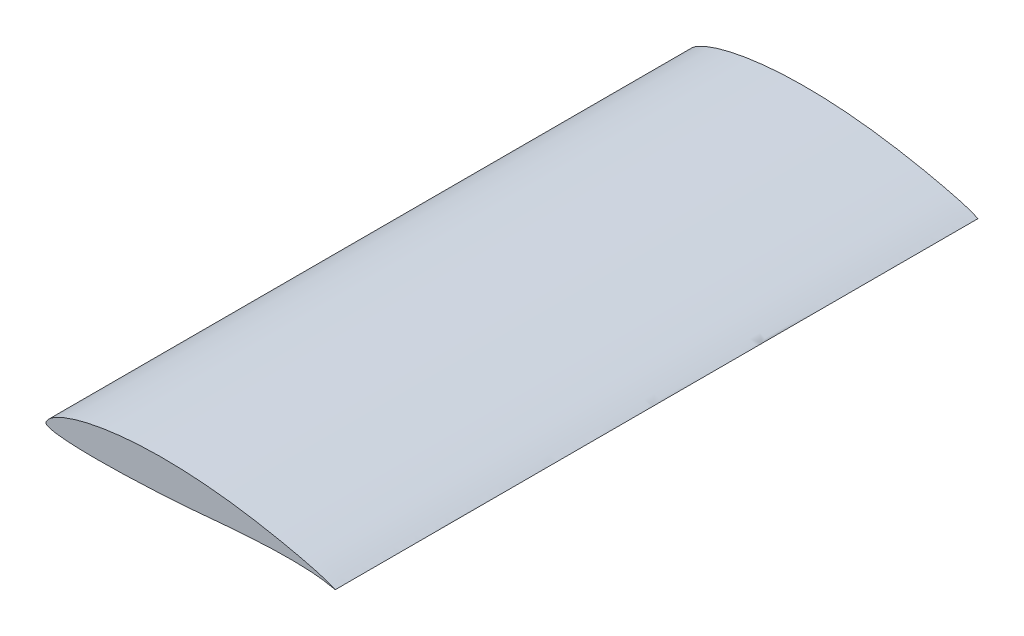
SolidWorks part; units mm, degrees
material "polystirene foam"
ref_plane "Front Plane" through (0, 0, 0) normal (0, 0, 1) x (1, 0, 0)
ref_plane "Top Plane" through (0, 0, 0) normal (0, 1, 0) x (1, 0, 0)
ref_plane "Right Plane" through (0, 0, 0) normal (1, 0, 0) x (0, 0, -1)
curve "Curve1"
  spline degree 3 poles (267.933, 0.5337, 0) (270.49, -0.1564, 0) (268.2375, 0.6665, 0) (266.5672, 1.4668, 0) (262.6756, 3.0154, 0) (257.9132, 4.5724, 0) (251.732, 6.3325, 0) (244.4112, 8.2376, 0) (235.9576, 10.2728, 0) (226.5142, 12.3893, 0) (216.1934, 14.5409, 0) (205.1313, 16.6775, 0) (193.4567, 18.7298, 0) (181.2977, 20.6324, 0) (168.7678, 22.3117, 0) (155.9753, 23.7079, 0) (143.0353, 24.8049, 0) (130.0617, 25.5802, 0) (117.1734, 26.0003, 0) (104.4837, 26.0576, 0) (92.1044, 25.7531, 0) (80.1395, 25.0742, 0) (68.69, 24.0381, 0) (57.8509, 22.6699, 0) (47.7143, 21.0125, 0) (38.3732, 19.0872, 0) (29.9084, 16.9558, 0) (22.399, 14.6444, 0) (15.9079, 12.2159, 0) (10.4843, 9.7202, 0) (6.177, 7.2209, 0) (2.9612, 4.7412, 0) (0.9766, 2.4261, 0) (0.0237, 0.7907, 0) (-0.0162, -0.4697, 0) (0.8003, -1.8361, 0) (3.4921, -2.6295, 0) (7.308, -3.6627, 0) (12.6566, -4.3991, 0) (19.3194, -5.0329, 0) (27.2905, -5.4698, 0) (36.4622, -5.7387, 0) (46.7414, -5.84, 0) (58.0105, -5.7702, 0) (70.1434, -5.5368, 0) (83.0071, -5.1408, 0) (96.4629, -4.5659, 0) (110.374, -3.827, 0) (124.6167, -2.893, 0) (139.0995, -1.7363, 0) (153.7348, -0.4008, 0) (168.4097, 0.8923, 0) (182.9339, 2.0414, 0) (197.0782, 2.9592, 0) (210.6044, 3.579, 0) (223.2667, 3.8744, 0) (234.8405, 3.8186, 0) (245.0477, 3.4533, 0) (253.7786, 2.7629, 0) (260.4407, 1.9422, 0) (265.7815, 0.9299, 0) (267.933, 0.5337, 0) (270.49, -0.1564, 0) (268.2375, 0.6665, 0) knots -0.016249 -0.007187 -0.001789 0 0.001694 0.006395 0.013462 0.022754 0.034367 0.048191 0.064031 0.081681 0.100894 0.121432 0.143025 0.165434 0.188439 0.211855 0.235496 0.259144 0.282615 0.305702 0.328232 0.35003 0.370944 0.390817 0.409506 0.426857 0.442733 0.457018 0.469615 0.48045 0.489472 0.49673 0.502329 0.506256 0.506442 0.509182 0.513914 0.521178 0.530944 0.543145 0.55767 0.574384 0.59311 0.613638 0.635744 0.659184 0.683714 0.709076 0.735036 0.76143 0.788184 0.815057 0.841645 0.867514 0.892232 0.915364 0.936485 0.9552 0.971104 0.983751 0.992813 0.998211 1 1.001694 1.006395 1.013462 periodic
sketch "Sketch1" plane through (0, 0, 0) normal (0, 0, 1) x (1, 0, 0)
  line L0 (270, 0) -> (0, 0) construction
  line L1 (0, -23.2448) -> (0, 51.8173) construction
  spline S1 degree 3 poles (133.9665, 0.2669) (135.245, -0.0782) (134.1188, 0.3333) (133.2836, 0.7334) (131.3378, 1.5077) (128.9566, 2.2862) (125.866, 3.1663) (122.2056, 4.1188) (117.9788, 5.1364) (113.2571, 6.1947) (108.0967, 7.2704) (102.5657, 8.3388) (96.7284, 9.3649) (90.6489, 10.3162) (84.3839, 11.1558) (77.9876, 11.854) (71.5176, 12.4024) (65.0308, 12.7901) (58.5867, 13.0001) (52.2418, 13.0288) (46.0522, 12.8766) (40.0697, 12.5371) (34.345, 12.019) (28.9254, 11.335) (23.8572, 10.5062) (19.1866, 9.5436) (14.9542, 8.4779) (11.1995, 7.3222) (7.954, 6.1079) (5.2422, 4.8601) (3.0885, 3.6104) (1.4806, 2.3706) (0.4883, 1.2131) (0.0119, 0.3954) (-0.0081, -0.2349) (0.4001, -0.918) (1.7461, -1.3148) (3.654, -1.8313) (6.3283, -2.1996) (9.6597, -2.5164) (13.6453, -2.7349) (18.2311, -2.8693) (23.3707, -2.92) (29.0052, -2.8851) (35.0717, -2.7684) (41.5036, -2.5704) (48.2314, -2.283) (55.187, -1.9135) (62.3083, -1.4465) (69.5497, -0.8682) (76.8674, -0.2004) (84.2049, 0.4461) (91.467, 1.0207) (98.5391, 1.4796) (105.3022, 1.7895) (111.6334, 1.9372) (117.4203, 1.9093) (122.5239, 1.7266) (126.8893, 1.3814) (130.2203, 0.9711) (132.8907, 0.4649) (133.9665, 0.2669) (135.245, -0.0782) (134.1188, 0.3333) knots -0.016249 -0.007187 -0.001789 0 0.001694 0.006395 0.013462 0.022754 0.034367 0.048191 0.064031 0.081681 0.100894 0.121432 0.143025 0.165434 0.188439 0.211855 0.235496 0.259144 0.282615 0.305702 0.328232 0.35003 0.370944 0.390817 0.409506 0.426857 0.442733 0.457018 0.469615 0.48045 0.489472 0.49673 0.502329 0.506256 0.506442 0.509182 0.513914 0.521178 0.530944 0.543145 0.55767 0.574384 0.59311 0.613638 0.635744 0.659184 0.683714 0.709076 0.735036 0.76143 0.788184 0.815057 0.841645 0.867514 0.892232 0.915364 0.936485 0.9552 0.971104 0.983751 0.992813 0.998211 1 1.001694 1.006395 1.013462 only from (135, 0) to (135, 0)
extrude "Boss-Extrude1" add sketch "Sketch1" along normal blind 300
